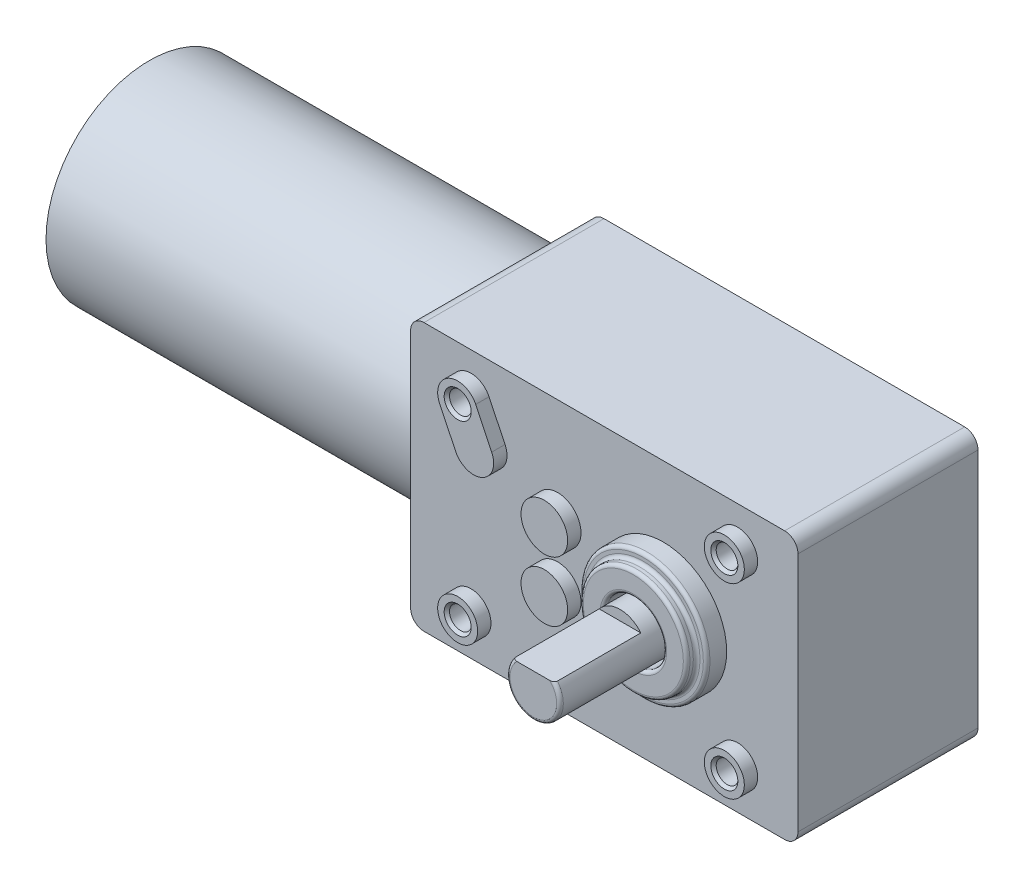
SolidWorks part; units mm, degrees
ref_plane "Alzado" through (0, 0, 0) normal (0, 0, 1) x (1, 0, 0)
ref_plane "Planta" through (0, 0, 0) normal (0, 1, 0) x (1, 0, 0)
ref_plane "Vista lateral" through (0, 0, 0) normal (1, 0, 0) x (0, 0, -1)
sketch "Croquis2" plane through (0, 0, 0) normal (0, 0, 1) x (1, 0, 0)
  line L0 (0, 0) -> (-76.1075, 0) construction
  line L1 (-57.2, 6) -> (-57.2, 15.5)
  line L2 (-57.2, 15.5) -> (0, 15.5)
  line L3 (0, 15.5) -> (0, 0)
  line L4 (0, 0) -> (-57.2, 0)
  line L5 (-57.2, 6) -> (-60.2, 6)
  line L6 (-60.2, 6) -> (-60.2, 0)
  line L7 (-60.2, 0) -> (-57.2, 0)
  dimension "D1" = 57.2
  dimension "D2" = 31
  dimension "D3" = 3
  dimension "D4" = 6
revolve "Revolución1" add sketch "Croquis2" angle 360 about L0
sketch "Croquis3" plane through (0, 0, 0) normal (0, 0, 1) x (1, 0, 0)
  line L0 (0, -15.5) -> (0, 15.5) construction
  line L1 (2, 20.055) -> (56.1, 20.055)
  line L2 (0, 18.055) -> (0, -18.055)
  line L3 (2, -20.055) -> (56.1, -20.055)
  line L4 (58.1, 18.055) -> (58.1, -18.055)
  line L5 (0, 20.055) -> (58.1, -20.055) construction
  line L6 (0, -20.055) -> (58.1, 20.055) construction
  line L7 (9.05, -14) -> (9.05, 14) construction
  line L8 (9.05, 14) -> (49.05, 14) construction
  line L9 (49.05, 14) -> (49.05, -14) construction
  line L10 (49.05, -14) -> (9.05, -14) construction
  line L11 (11.45, 15.4173) -> (11.45, 6.308) construction
  line L14 (9.05, 14) -> (11.45, 9) construction
  line L15 (6.1752, 9) -> (13.5213, 9) construction
  line L16 (11.7546, 15.2982) -> (14.1546, 10.2982)
  line L17 (6.3454, 12.7018) -> (8.7454, 7.7018)
  arc A0 (0, -18.055) -> (2, -20.055) centre (2, -18.055) ccw
  arc A1 (56.1, -20.055) -> (58.1, -18.055) centre (56.1, -18.055) ccw
  arc A2 (56.1, 20.055) -> (58.1, 18.055) centre (56.1, 18.055) cw
  arc A3 (2, 20.055) -> (0, 18.055) centre (2, 18.055) ccw
  circle A5 centre (49.05, 14) radius 3
  circle A6 centre (49.05, -14) radius 3
  circle A7 centre (9.05, -14) radius 3
  arc A9 (11.7546, 15.2982) -> (6.3454, 12.7018) centre (9.05, 14) ccw
  arc A12 (8.7454, 7.7018) -> (14.1546, 10.2982) centre (11.45, 9) ccw
  circle A13 centre (22.05, 4.5) radius 3.5
  circle A14 centre (22.05, -4.5) radius 3.5
  circle A15 centre (37.9, 0) radius 9.5 construction
  point P0 (29.05, 0)
  point P31 (11.45, 9)
  point P32 (10.25, 11.5)
  point P44 (0, 0)
  dimension "D3" = 2
  dimension "D8" = 6
  dimension "D9" = 2.4
  dimension "D10" = 5
  dimension "D11" = 3
  dimension "D12" = 6
  dimension "D14" = 19
  dimension "D15" = 7
  dimension "D16" = 7
  dimension "D17" = 9
  dimension "D18" = 4.5
  dimension "D1" = 40.11
  dimension "D2" = 58.1
  dimension "D4" = 28
  dimension "D5" = 14
  dimension "D6" = 40
  dimension "D7" = 20
  dimension "D13" = 37.9
extrude "Saliente-Extruir1" add sketch "Croquis3" along normal blind 18 and the other way blind 9 separate body contours L1 A2 L4 A1 L3 A0 L2 A3
extrude "Saliente-Extruir2" add sketch "Croquis3<3>" along normal blind 20 and the other way blind 11 contours L17 A12 L16 A9 | A5 | A6 | A7 | A13 | A14 region at (10.25, 11.5, 0) region at (49.05, 14, 0) region at (49.05, -14, 0) region at (9.05, -14, 0)
sketch "Croquis3<3>" plane through (0, 0, 0) normal (0, 0, 1) x (1, 0, 0) same geometry as "Croquis3"
ref_plane "Plano1" through (37.9, 0, 0) normal (-1, 0, 0) x (0, 0, 1)
sketch "Croquis4" plane through (37.9, 0, 0) normal (-1, 0, 0) x (0, 0, 1)
  line L0 (18, 0) -> (-15.5, 0) construction
  line L1 (18, 18.055) -> (18, -18.055) construction
  line L2 (37.5, 0) -> (37.5, 3.5)
  line L3 (37, 4) -> (18, 4)
  line L5 (22, 8) -> (21.5, 8)
  line L6 (21, 8.5) -> (21, 9)
  line L7 (20.5, 9.5) -> (-11.5, 9.5)
  line L9 (18, 0) -> (37.5, 0)
  line L11 (18, 4) -> (18, 4.5)
  line L12 (18, 1) -> (18, 8) construction
  line L13 (18, 4.5) -> (22, 4.5)
  line L14 (22.5, 5) -> (22.5, 7.5)
  line L15 (-12, 9) -> (-12, 8.5)
  line L17 (-12.5, 8) -> (-13, 8)
  line L18 (-13.5, 7.5) -> (-13.5, 4.25)
  line L19 (-13, 3.75) -> (-9, 3.75)
  line L20 (-9, 3.75) -> (-9, 0)
  line L21 (-9, 0) -> (18, 0)
  circle A0 centre (0, 0) radius 15.5 construction
  arc A1 (-13.5, 4.25) -> (-13, 3.75) centre (-13, 4.25) ccw
  arc A2 (-13, 8) -> (-13.5, 7.5) centre (-13, 7.5) ccw
  arc A3 (-12, 8.5) -> (-12.5, 8) centre (-12.5, 8.5) cw
  arc A4 (-11.5, 9.5) -> (-12, 9) centre (-11.5, 9) ccw
  arc A5 (37.5, 3.5) -> (37, 4) centre (37, 3.5) ccw
  arc A6 (22, 4.5) -> (22.5, 5) centre (22, 5) ccw
  arc A7 (22.5, 7.5) -> (22, 8) centre (22, 7.5) ccw
  arc A8 (21.5, 8) -> (21, 8.5) centre (21.5, 8.5) cw
  arc A9 (21, 9) -> (20.5, 9.5) centre (20.5, 9) ccw
  point P25 (-13.5, 3.75)
  point P28 (-13.5, 8)
  point P31 (-12, 8)
  point P36 (37.5, 4)
  point P39 (22.5, 4.5)
  point P42 (22.5, 8)
  point P45 (21, 8)
  dimension "D14" = 0.5
  dimension "D1" = 19
  dimension "D2" = 16
  dimension "D3" = 1.5
  dimension "D4" = 1.5
  dimension "D5" = 36
  dimension "D6" = 19.5
  dimension "D7" = 15
  dimension "D8" = 8
  dimension "D9" = 3.5
  dimension "D10" = 0.5
  dimension "D11" = 16
  dimension "D12" = 7.5
  dimension "D13" = 4.5
revolve "Revolución2" add sketch "Croquis4" angle 360 about L0
sketch "Croquis5" plane through (0, 0, 37.5) normal (0, 0, 1) x (1, 0, 0)
  line L0 (34.7775, 2.5) -> (41.0225, 2.5)
  line L1 (37.9, 14.85) -> (37.9, -14.85) construction
  arc A0 (41.0225, 2.5) -> (34.7775, 2.5) centre (37.9, 0) ccw
  circle A1 centre (37.9, 0) radius 4 construction
  point P1 (37.9, -4)
  dimension "D2" = 4
  dimension "D1" = 6.5
extrude "Cortar-Extruir1" cut sketch "Croquis5" against normal blind 13
hole_wizard "Taladro roscado M4x0.71" positions "Croquis6" profile "Croquis7" tap size "M4x0.7" standard "Ansi Metric"
sketch "Croquis6" plane through (0, 0, 20) normal (0, 0, 1) x (1, 0, 0)
  point P0 (9.05, 14)
  point P2 (49.05, 14)
  point P4 (49.05, -14)
  point P6 (9.05, -14)
  point P9 (0, 0)
  point P14 (9.05, 14)
  point P16 (49.05, 14)
  point P18 (49.05, -14)
  point P20 (9.05, -14)
sketch "Croquis7" plane through (9.05, 14, 20) normal (1, 0, 0) x (0, -1, 0)
  line L0 (0, 0) -> (0, 8.4914)
  line L1 (0, 8.4914) -> (1.65, 7.5)
  line L2 (1.65, 7.5) -> (1.65, 0.4314)
  line L3 (1.65, 0.4314) -> (2.025, 0)
  line L5 (2.025, 0) -> (0, 0)
  line L6 (-1.65, 0.4314) -> (-2.025, 0) construction
  line L10 (0, 8.4914) -> (-1.65, 7.5) construction
  line L11 (0, -6.35) -> (0, 107.95) construction
  dimension "Diámetro de perforador para roscar" = 3.3
  dimension "Profundidad de perforador para roscar" = 7.5
  dimension "Diámetro de avellanado cercano" = 4.05
  dimension "Ángulo de avellanado cercano" = 82
  dimension "Ángulo de perforador" = 118
cosmetic thread "Rosca de taladro1" parameters "D1"=7.5, "D2"=4
cosmetic thread "Rosca de taladro2" parameters "D1"=7.5, "D2"=4
cosmetic thread "Rosca de taladro3" parameters "D1"=7.5, "D2"=4
cosmetic thread "Rosca de taladro4" parameters "D1"=7.5, "D2"=4
